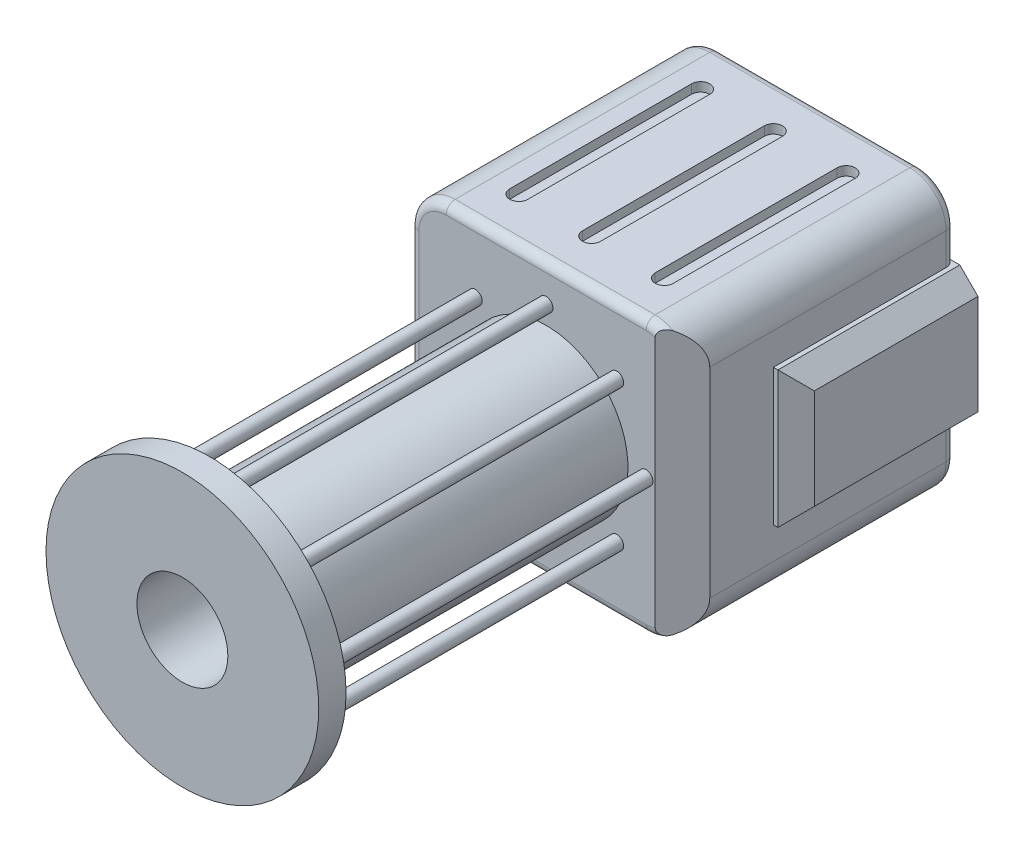
SolidWorks part; units mm, degrees
ref_plane "Front Plane" through (0, 0, 0) normal (0, 0, 1) x (1, 0, 0)
ref_plane "Top Plane" through (0, 0, 0) normal (0, 1, 0) x (1, 0, 0)
ref_plane "Right Plane" through (0, 0, 0) normal (1, 0, 0) x (0, 0, -1)
sketch "Sketch1" plane through (0, 0, 0) normal (0, 0, 1) x (1, 0, 0)
  line L1 (-15, 15) -> (15, 15)
  line L2 (-15, 15) -> (-15, -15)
  line L3 (-15, -15) -> (15, -15)
  line L4 (15, 15) -> (15, -15)
  line L5 (-15, 15) -> (15, -15) construction
  line L6 (-15, -15) -> (15, 15) construction
  point P0 (0, 0)
  dimension "D1" = 30
extrude "Boss-Extrude1" add sketch "Sketch1" along normal mid plane 30
sketch "Sketch2" plane through (0, 0, 0) normal (1, 0, 0) x (0, 0, -1)
  line L0 (-15, 0) -> (-55, 0) construction
  line L1 (-15, -15) -> (-15, 15) construction
  line L2 (16.5, 0) -> (-16.5, 0) construction
  line L3 (-55, 0) -> (-55, 15)
  line L4 (-55, 15) -> (-52, 15)
  line L5 (-52, 15) -> (-52, 9)
  line L6 (-52, 9) -> (-15, 9)
  line L7 (-15, 9) -> (-15, 0)
  line L8 (-15, 0) -> (-55, 0)
  dimension "D1" = 18
  dimension "D2" = 3
  dimension "D3" = 40
  dimension "D4" = 15
revolve "Revolve1" add sketch "Sketch2" angle 360 about L0
fillet "Fillet1" radius 4 4 edges at (-15, 15, 0) (-15, -15, 0) (15, -15, 0) (15, 15, 0)
chamfer "Chamfer2" distance 3 angle 45 1 edges at (15, 0, 15) tangent propagation no
fillet "Fillet2" radius 1 15 edges at (13.8284, 13.8284, -15) (15, 0, -15) (13.8284, -13.8284, -15) (0, -15, -15) (-13.8284, -13.8284, -15) (-15, 0, -15) (-13.8284, 13.8284, -15) (11.504, 14.9681, 15) (11.504, -14.9681, 15) (0, -15, 15) (-13.8284, -13.8284, 15) (-15, 0, 15) (-13.8284, 13.8284, 15) (0, 15, -15) (0, 15, 15)
sketch "Sketch3" plane through (0, 0, -15) normal (0, 0, -1) x (-1, 0, 0)
  circle A0 centre (0, 0) radius 10
  dimension "D1" = 20
extrude "Boss-Extrude2" add sketch "Sketch3" along normal blind 5
fillet "Fillet3" radius 5 1 edges at (-10, 0, -20)
sketch "Sketch4" plane through (0, 0, -15) normal (0, 0, -1) x (-1, 0, 0)
  line L0 (-15, -11) -> (-15, 11) construction
  line L2 (-12.5, -7.5) -> (-17.5, -7.5)
  line L3 (-12.5, -7.5) -> (-12.5, 7.5)
  line L4 (-12.5, 7.5) -> (-17.5, 7.5)
  line L5 (-17.5, -7.5) -> (-17.5, 7.5)
  line L6 (-12.5, -7.5) -> (-17.5, 7.5) construction
  line L7 (-12.5, 7.5) -> (-17.5, -7.5) construction
  point P2 (-15, 0)
  dimension "D1" = 15
  dimension "D2" = 5
extrude "Boss-Extrude3" add sketch "Sketch4" against normal blind 20
chamfer "Chamfer3" distance 2 angle 45 3 edges at (17.5, -7.5, -5) (17.5, 7.5, -5) (17.5, 0, 5)
sketch "Sketch5" plane through (0, 0, 55) normal (0, 0, 1) x (1, 0, 0)
  circle A0 centre (0, 0) radius 5
  dimension "D1" = 10
extrude "Cut-Extrude1" cut sketch "Sketch5" against normal blind 10
sketch "Sketch6" plane through (0, 0, 55) normal (0, 0, 1) x (1, 0, 0)
  line L0 (0, 0) -> (0, 11) construction
  circle A0 centre (0, 11) radius 0.75
  point P4 (0, 0)
  dimension "D1" = 1.5
  dimension "D2" = 11
extrude "Boss-Extrude5" add sketch "Sketch6" against normal up to surface (40 mm away) contours A0 up to face at (-0.6535, 0, 15)
pattern_circular "CirPattern2" count 8 over 360 about axis through (0, 0, 55) along (0, 0, -1) of "Boss-Extrude5"
sketch "Sketch7" plane through (-15, 0, 0) normal (-1, 0, 0) x (0, 0, 1)
  circle A0 centre (0, 0) radius 5
  dimension "D1" = 10
extrude "Cut-Extrude2" cut sketch "Sketch7" against normal blind 10
sketch "Sketch8" plane through (0, 15, 0) normal (0, 1, 0) x (1, 0, 0)
  line L0 (0, -10) -> (0, 10) construction
  line L1 (-1, -10) -> (-1, 10)
  line L2 (1, -10) -> (1, 10)
  arc A0 (-1, -10) -> (1, -10) centre (0, -10) ccw
  arc A1 (1, 10) -> (-1, 10) centre (0, 10) ccw
  point P2 (0, 0)
  dimension "D1" = 2
  dimension "D2" = 20
extrude "Cut-Extrude3" cut sketch "Sketch8" against normal blind 1
pattern_linear "LPattern1" count 2 spacing 8 along (-1, 0, 0) count 2 spacing 8 along (1, 0, 0) of "Cut-Extrude3"
